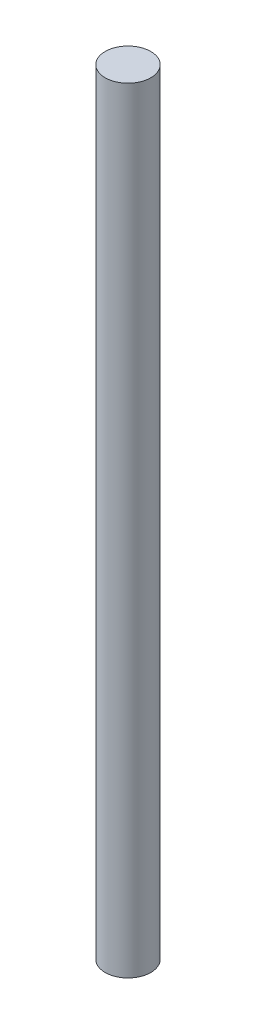
SolidWorks part; units mm, degrees
material "炭素鋼(普通)"
ref_plane "VERT" through (0, 0, 0) normal (0, 0, 1) x (1, 0, 0)
ref_plane "HOR" through (0, 0, 0) normal (0, 1, 0) x (1, 0, 0)
ref_plane "CTR" through (0, 0, 0) normal (1, 0, 0) x (0, 0, -1)
ref_axis "A_X" through (5.5, 0, 0) along (-1, 0, 0)
ref_axis "A_Y" through (0, 178.5, 0) along (0, -1, 0)
ref_axis "A_Z" through (0, 0, 5.5) along (0, 0, -1)
sketch3d "PNT_CG"
  point P0 (0, 0, 0)
sketch "Sketch1" plane through (0, 0, 0) normal (0, 1, 0) x (1, 0, 0)
  circle A0 centre (0, 0) radius 5
  dimension "D1" = 10
extrude "Boss-Extrude1" add sketch "Sketch1" along normal blind 170
